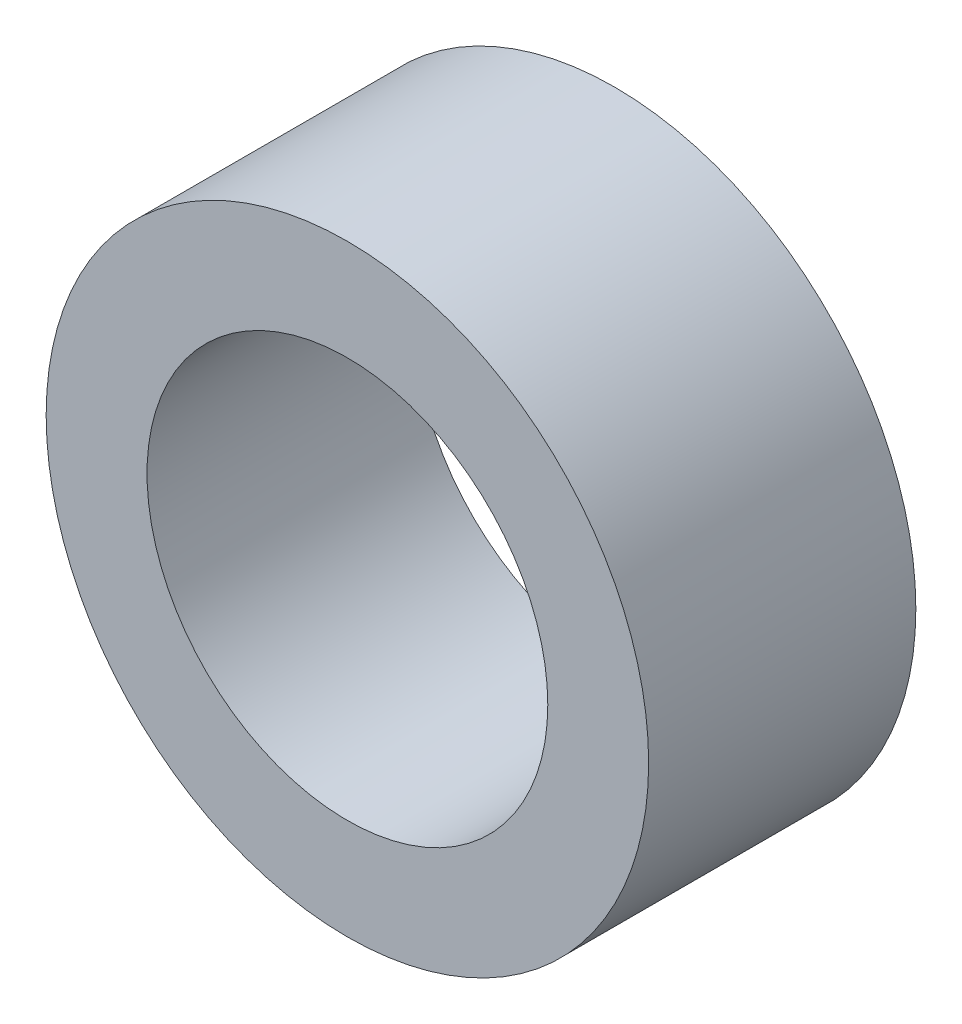
SolidWorks part; units mm, degrees
material "Brass"
ref_plane "Front Plane" through (0, 0, 0) normal (0, 0, 1) x (1, 0, 0)
ref_plane "Top Plane" through (0, 0, 0) normal (0, 1, 0) x (1, 0, 0)
ref_plane "Right Plane" through (0, 0, 0) normal (1, 0, 0) x (0, 0, -1)
sketch "Sketch1" plane through (0, 0, 0) normal (0, 0, 1) x (1, 0, 0)
  circle A0 centre (0, 0) radius 4.51
  circle A1 centre (0, 0) radius 3
  dimension "D1" = 9.02
  dimension "ID" = 6
extrude "Extrude1" add sketch "Sketch1" along normal mid plane 4
sketch "Sketch2" plane through (0, 0, 0) normal (1, 0, 0) x (0, 0, -1)
  line L0 (-2, -3) -> (2, -3) construction
  line L3 (2, 3) -> (-2, 3) construction
  line L5 (-2, -3) -> (2, -3)
  line L6 (2, 3) -> (-2, 3)
sketch "Sketch4" plane through (0, 0, 2) normal (0, 0, 1) x (1, 0, 0)
  line L0 (0, 0) -> (-2.1213, 2.1213)
  line L1 (0, -3.3) -> (0, 3.3) construction
  circle A0 centre (0, 0) radius 3 construction
  dimension "D1" = 45
ref_axis "Center Axis 1" through (0, 0, -22) along (0, 0, 1)
ref_plane "Contaxt Plane 1" through (0, 0, 2) normal (0, 0, 1) x (1, 0, 0)
ref_plane "Contact Plane 2" through (0, 0, -2) normal (0, 0, -1) x (-1, 0, 0)
